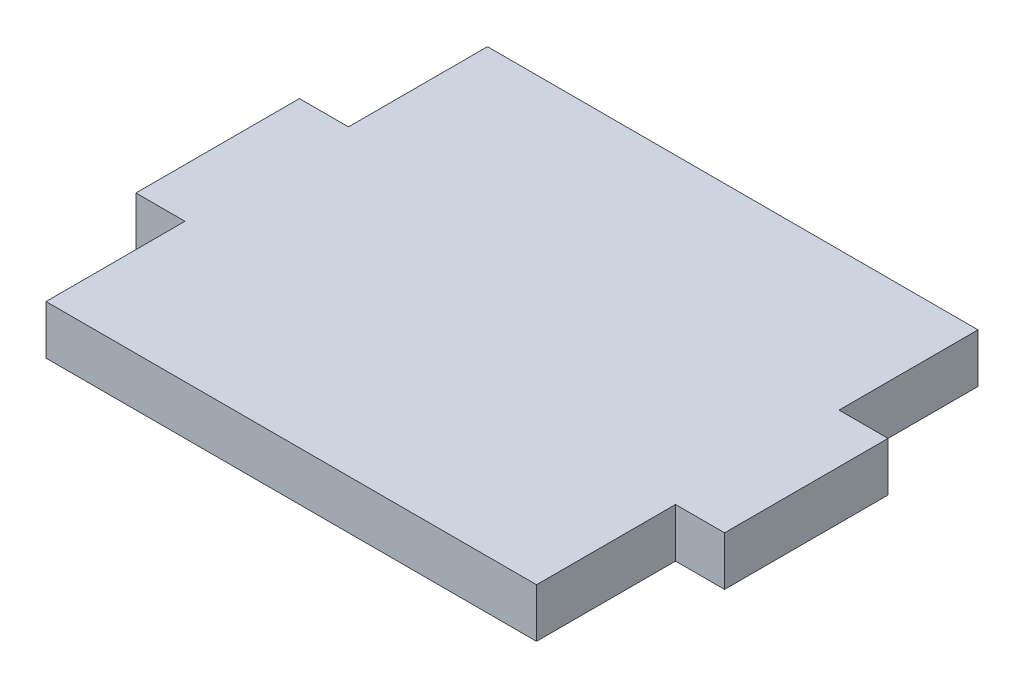
SolidWorks part; units mm, degrees
ref_plane "Alzado" through (0, 0, 0) normal (0, 0, 1) x (1, 0, 0)
ref_plane "Planta" through (0, 0, 0) normal (0, 1, 0) x (1, 0, 0)
ref_plane "Vista lateral" through (0, 0, 0) normal (1, 0, 0) x (0, 0, -1)
sketch "Croquis1" plane through (0, 0, 0) normal (0, 1, 0) x (1, 0, 0)
  line L0 (0, 0) -> (30, 0)
  line L1 (0, 0) -> (0, 8.5)
  line L2 (0, 27) -> (30, 27)
  line L3 (30, 27) -> (30, 18.5)
  line L5 (-3, 13.5) -> (-3, 18.5)
  line L6 (-3, 18.5) -> (0, 18.5)
  line L7 (-3, 13.5) -> (-3, 8.5)
  line L8 (-3, 8.5) -> (0, 8.5)
  line L10 (33, 8.5) -> (30, 8.5)
  line L11 (33, 13.5) -> (33, 8.5)
  line L12 (33, 18.5) -> (30, 18.5)
  line L13 (33, 13.5) -> (33, 18.5)
  line L14 (30, 8.5) -> (30, 0)
  line L15 (0, 18.5) -> (0, 27)
  dimension "D1" = 30
  dimension "D2" = 27
  dimension "D4" = 5
  dimension "D5" = 5
extrude "Saliente-Extruir1" add sketch "Croquis1" along normal blind 3
